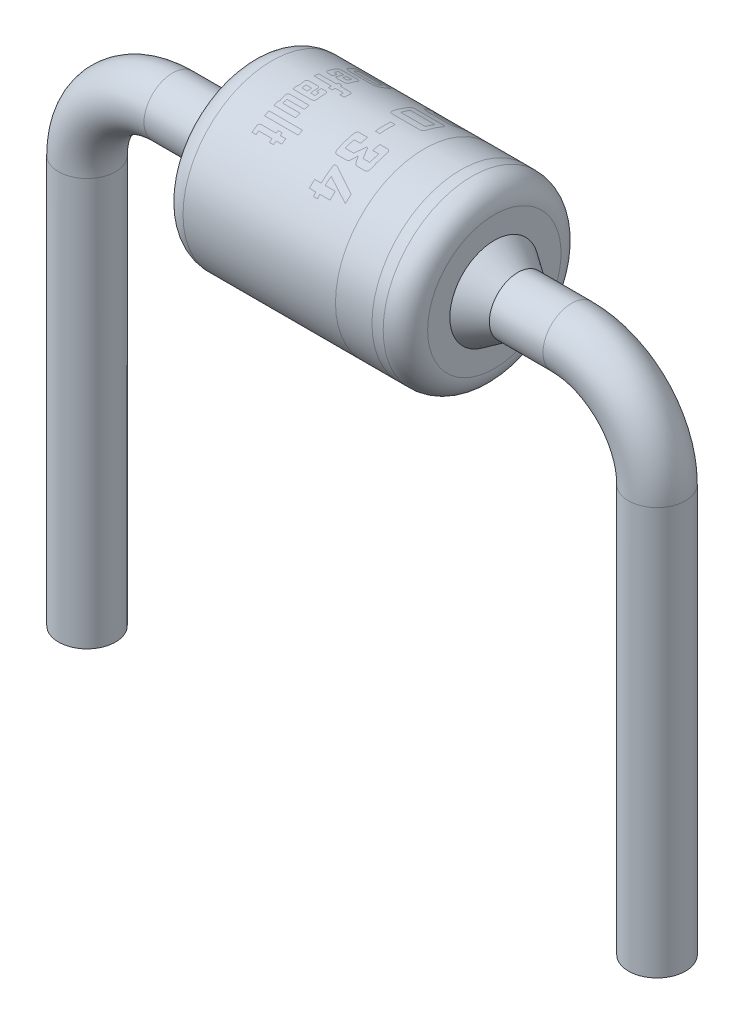
SolidWorks part; units mm, degrees
ref_plane "Front Plane" through (0, 0, 0) normal (0, 0, 1) x (1, 0, 0)
ref_plane "Top Plane" through (0, 0, 0) normal (0, 1, 0) x (1, 0, 0)
ref_plane "Right Plane" through (0, 0, 0) normal (1, 0, 0) x (0, 0, -1)
ref_plane "BODY_RPlane" through (2.54, 0, 0) normal (1, 0, 0) x (0, 0, -1)
sketch "Sketch10" plane through (0, 0, 0) normal (0, 0, 1) x (1, 0, 0)
  line L0 (1.24, 1.7925) -> (3.84, 1.7925) construction
  line L1 (2.54, -0.8886) -> (2.54, 0.8886) construction
  line L2 (1.45, 2.1888) -> (2.54, 2.1888) construction
  line L3 (1.45, 2.6995) -> (1.45, 2.1082) construction
  line L4 (1.6481, 2.585) -> (3.4319, 2.585)
  line L6 (1.45, 2.3869) -> (1.45, 2.1888)
  line L7 (1.45, 2.1888) -> (3.63, 2.1888)
  line L8 (3.63, 2.3869) -> (3.63, 2.1888)
  arc A2 (1.6481, 2.585) -> (1.45, 2.3869) centre (1.6481, 2.3869) ccw
  arc A3 (3.4319, 2.585) -> (3.63, 2.3869) centre (3.4319, 2.3869) cw
  point P2 (2.54, 1.7925)
  point P14 (2.54, 2.585)
  point P15 (2.54, 2.1888)
  point P18 (2.54, 2.585)
  dimension "D6" = 0.1981
  dimension "D1" = 1.7925
  dimension "D2" = 2.6
  dimension "D4" = 0.7925
  dimension "D5" = 0.21
  dimension "D3" = 0.3962
revolve "BODY_main" add sketch "Sketch10" angle 360 about L0
sketch "Sketch11" plane through (0, 0, 0) normal (0, 0, 1) x (1, 0, 0)
  line L0 (1.24, 1.7925) -> (1.24, 2.0465)
  line L1 (1.24, 2.0465) -> (1.45, 2.1888)
  line L2 (1.45, 2.1888) -> (1.65, 2.1888)
  line L3 (1.24, 1.7925) -> (1.65, 1.7925)
  line L5 (1.65, 1.7925) -> (1.65, 2.1888)
  line L9 (2.54, -0.8886) -> (2.54, 0.8886) construction
  line L12 (3.43, 1.7925) -> (3.43, 2.1888)
  line L13 (3.84, 1.7925) -> (3.43, 1.7925)
  line L14 (3.63, 2.1888) -> (3.43, 2.1888)
  line L15 (3.84, 2.0465) -> (3.63, 2.1888)
  line L16 (3.84, 1.7925) -> (3.84, 2.0465)
revolve "BODY_to_PIN" add sketch "Sketch11" angle 360 about L0
ref_plane "TEXT_plane" through (0, 2.685, 0) normal (0, 1, 0) x (1, 0, 0)
sketch "Sketch4"
  dimension "D4" = 5.08
  dimension "D1" = 4.9794
  dimension "D3" = 0.325
  dimension "D5" = 0.1
  dimension "D6" = 0.15
  dimension "D2" = 5
wrap "TEXT_Wrap" sketch "Sketch4" wrap type scribe source sketch "Sketch4" face at (1.6481, 1.7925, 0.7925)
sketch "Sketch6" plane through (2.54, 0, 0) normal (1, 0, 0) x (0, 0, -1)
  circle A0 centre (0, 1.7925) radius 0.254
  dimension "D1" = 0.508
sketch "Sketch7" plane through (0, 0, 0) normal (0, 0, 1) x (1, 0, 0)
  line L0 (4.318, 1.7925) -> (0.762, 1.7925)
  line L1 (0, 1.0305) -> (0, -2.6)
  line L2 (2.54, 1.7925) -> (2.54, -2.6) construction
  line L3 (0, -2.6) -> (2.54, -2.6) construction
  line L5 (2.54, -0.8886) -> (2.54, 0.8886) construction
  line L6 (5.08, 1.0305) -> (5.08, -2.6)
  line L9 (1.24, 1.7925) -> (3.84, 1.7925) construction
  arc A0 (0.762, 1.7925) -> (0, 1.0305) centre (0.762, 1.0305) ccw
  arc A1 (4.318, 1.7925) -> (5.08, 1.0305) centre (4.318, 1.0305) cw
  dimension "D3" = 0.762
  dimension "D1" = 2.6
sweep "PINS" add profiles "Sketch6" path "Sketch7"
equation "\"D4@Sketch7\"=\"PIN_PITCH\""
equation "\"pin_config-----------------\"= 0x000000000000000000000000000000000"
equation "\"PIN_PITCH\"= 200mil"
equation "\"PCB_standoff\"= 1mm"
equation "\"PCB_thickness\"= 1.6mm"
equation "\"PCB_bottom_lead\"= 1.0mm"
equation "\"PIN_C_max\"= 0.558mm"
equation "\"PIN_C_min\"= 0.458mm"
equation "\"body_config----------------\"= 0x000000000000000000000000000000000"
equation "\"BODY_B_max\"= 3.04mm"
equation "\"BODY_B_min\"= 2.16mm"
equation "\"BODY_D_max\"= 1.9mm"
equation "\"BODY_D_min\"= 1.27mm"
equation "\"part_config----------------\"= 0x000000000000000000000000000000000"
equation "\"Component_Size\"= 1"
equation "\"Component_Type\"= 0'variable is not used"
equation "\"auto_calc-------------------\"= 0x000000000000000000000000000000000"
equation "\"BODY_B\"= IIF ( \"Component_Size\" > 0 , IIF ( \"Component_Size\" = 1 , ( ( \"BODY_B_max\" + \"BODY_B_min\" ) / 2 ) , \"BODY_B_max\" ) , \"BODY_B_min\" )'NOT_FOR_USER , AUTOMATIC CALCULATION"
equation "\"BODY_D\"= IIF ( \"Component_Size\" > 0 , IIF ( \"Component_Size\" = 1 , ( ( \"BODY_D_max\" + \"BODY_D_min\" ) / 2 ) , \"BODY_D_max\" ) , \"BODY_D_min\" )'NOT_FOR_USER , AUTOMATIC CALCULATION"
equation "\"PIN_C\"= IIF ( \"Component_Size\" > 0 , IIF ( \"Component_Size\" = 1 , ( ( \"PIN_C_max\" + \"PIN_C_min\" ) / 2 ) , \"PIN_C_max\" ) , \"PIN_C_min\" )'NOT_FOR_USER , AUTOMATIC CALCULATION"
equation "\"PIN_L\"= \"PCB_thickness\" + \"PCB_bottom_lead\"'NOT_FOR_USER , AUTOMATIC CALCULATION"
equation "\"PIN_R\"= \"PIN_C\" * 1.5'NOT_FOR_USER , AUTOMATIC CALCULATION"
equation "\"D1@BODY_RPlane\" = \"PIN_PITCH\" / 2"
equation "\"D1@TEXT_plane\"=\"BODY_D\"+\"PCB_standoff\"+0.1"
equation "\"D1@Sketch4\"=\"BODY_D\" * pi"
equation "\"BODY_CATM_H1\"= \"BODY_B\" / 8'NOT_FOR_USER , AUTOMATIC CALCULATION"
equation "\"D4@Sketch4\"=\"PIN_PITCH\""
equation "\"D1@Sketch6\"=\"PIN_C\""
equation "\"D3@Sketch7\"=\"PIN_R\""
equation "\"D1@Sketch7\"=\"PIN_L\""
equation "\"D2@Sketch10\"=\"BODY_B\""
equation "\"D1@Sketch10\"=(\"BODY_D\" / 2) + \"PCB_standoff\""
equation "\"D4@Sketch10\"=\"BODY_D\"/2"
equation "\"D1@Sketch11\"=\"PIN_C\"/2"
equation "\"D3@Sketch4\"=\"BODY_CATM_H1\""
equation "\"D3@Sketch10\"=\"BODY_D\"/4"
equation "\"D6@Sketch10\"=\"BODY_D\"/8"
